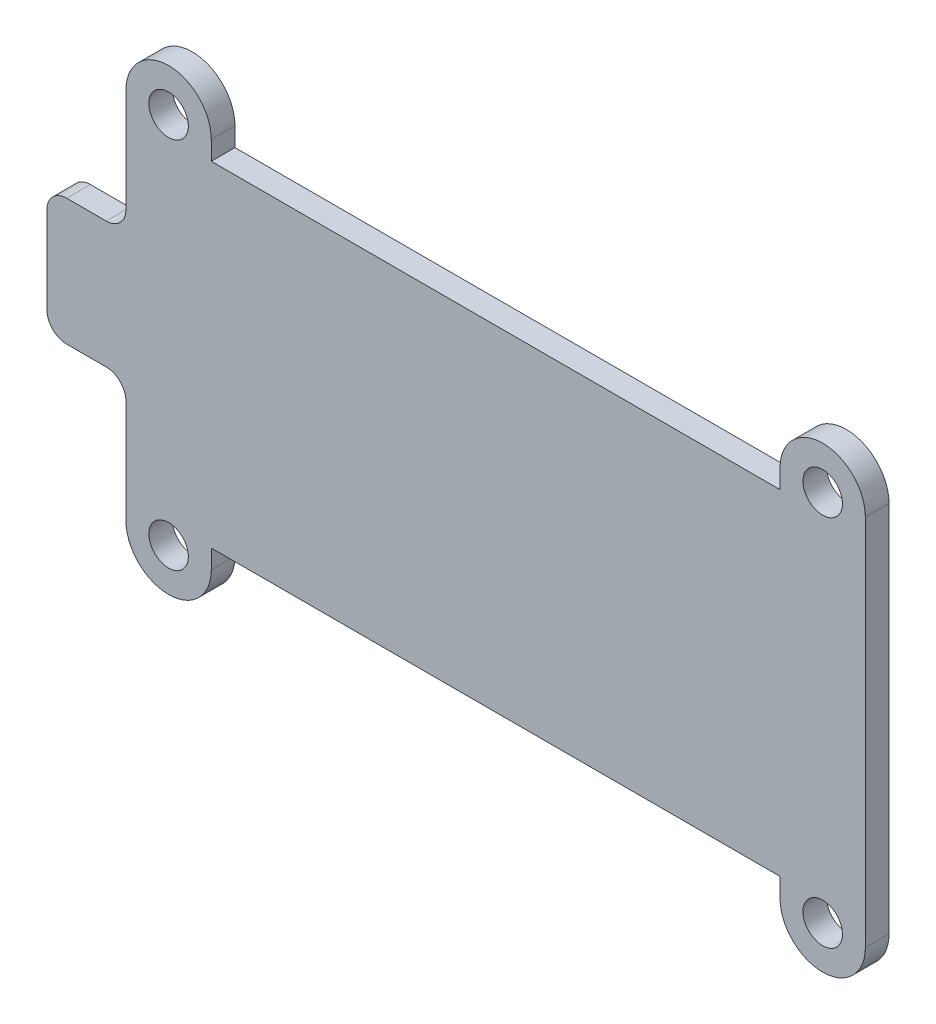
SolidWorks part; units mm, degrees
ref_plane "Front Plane" through (0, 0, 0) normal (0, 0, 1) x (1, 0, 0)
ref_plane "Top Plane" through (0, 0, 0) normal (0, 1, 0) x (1, 0, 0)
ref_plane "Right Plane" through (0, 0, 0) normal (1, 0, 0) x (0, 0, -1)
sketch "Sketch1" plane through (0, 0, 0) normal (0, 0, 1) x (1, 0, 0)
  line L0 (-24.65, 4) -> (-27.15, 4) construction
  line L1 (-28.4, 2.75) -> (-28.4, 2) construction
  line L7 (23.4, 3.8) -> (23.4, 11.8) construction
  line L8 (18, 11.8) -> (18, 10.6) construction
  line L9 (18, 10.6) -> (-18, 10.6) construction
  line L10 (-18, 10.6) -> (-18, 11.8) construction
  line L11 (-23.4, 11.8) -> (-23.4, 5.25) construction
  line L12 (-28.4, -2) -> (-28.4, -2.75) construction
  line L13 (-27.15, -4) -> (-24.65, -4) construction
  line L14 (-23.4, -5.25) -> (-23.4, -11.8) construction
  line L15 (-18, -11.8) -> (-18, -10.6) construction
  line L16 (-18, -10.6) -> (18, -10.6) construction
  line L17 (18, -10.6) -> (18, -11.8) construction
  line L18 (23.4, -11.8) -> (23.4, -3.8) construction
  line L24 (-24.65, 4) -> (-27.15, 4)
  line L25 (-28.4, 2.75) -> (-28.4, 2)
  line L31 (23.4, 3.8) -> (23.4, 11.8)
  line L32 (18, 11.8) -> (18, 10.6)
  line L33 (18, 10.6) -> (-18, 10.6)
  line L34 (-18, 10.6) -> (-18, 11.8)
  line L35 (-23.4, 11.8) -> (-23.4, 5.25)
  line L36 (-28.4, -2) -> (-28.4, -2.75)
  line L37 (-27.15, -4) -> (-24.65, -4)
  line L38 (-23.4, -5.25) -> (-23.4, -11.8)
  line L39 (-18, -11.8) -> (-18, -10.6)
  line L40 (-18, -10.6) -> (18, -10.6)
  line L41 (18, -10.6) -> (18, -11.8)
  line L42 (23.4, -11.8) -> (23.4, -3.8)
  line L48 (-28.4, -2) -> (-28.4, 2)
  line L49 (23.4, -3.8) -> (23.4, 3.8)
  arc A0 (-27.15, 4) -> (-28.4, 2.75) centre (-27.15, 2.75) ccw construction
  arc A1 (23.4, 11.8) -> (18, 11.8) centre (20.7, 11.8) ccw construction
  arc A2 (-18, 11.8) -> (-23.4, 11.8) centre (-20.7, 11.8) ccw construction
  arc A3 (-24.65, 4) -> (-23.4, 5.25) centre (-24.65, 5.25) ccw construction
  arc A4 (-28.4, -2.75) -> (-27.15, -4) centre (-27.15, -2.75) ccw construction
  arc A5 (-23.4, -5.25) -> (-24.65, -4) centre (-24.65, -5.25) ccw construction
  arc A6 (-23.4, -11.8) -> (-18, -11.8) centre (-20.7, -11.8) ccw construction
  arc A7 (18, -11.8) -> (23.4, -11.8) centre (20.7, -11.8) ccw construction
  arc A8 (-27.15, 4) -> (-28.4, 2.75) centre (-27.15, 2.75) ccw
  arc A9 (23.4, 11.8) -> (18, 11.8) centre (20.7, 11.8) ccw
  arc A10 (-18, 11.8) -> (-23.4, 11.8) centre (-20.7, 11.8) ccw
  arc A11 (-24.65, 4) -> (-23.4, 5.25) centre (-24.65, 5.25) ccw
  arc A12 (-28.4, -2.75) -> (-27.15, -4) centre (-27.15, -2.75) ccw
  arc A13 (-23.4, -5.25) -> (-24.65, -4) centre (-24.65, -5.25) ccw
  arc A14 (-23.4, -11.8) -> (-18, -11.8) centre (-20.7, -11.8) ccw
  arc A15 (18, -11.8) -> (23.4, -11.8) centre (20.7, -11.8) ccw
  circle A16 centre (-20.7, 11.8) radius 1.25
  circle A17 centre (20.7, 11.8) radius 1.25
  circle A18 centre (20.7, -11.8) radius 1.25
  circle A19 centre (-20.7, -11.8) radius 1.25
  dimension "D1" = 2.5
extrude "Boss-Extrude1" add sketch "Sketch1" along normal blind 1.5
